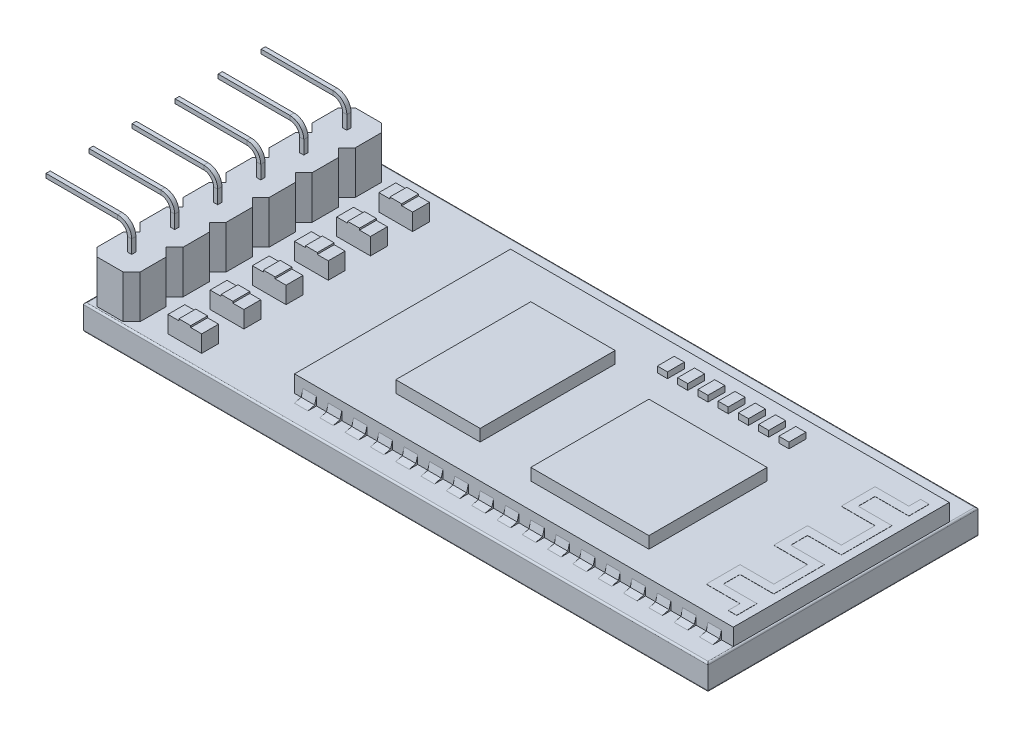
SolidWorks part; units mm, degrees
ref_plane "Front Plane" through (0, 0, 0) normal (0, 0, 1) x (1, 0, 0)
ref_plane "Top Plane" through (0, 0, 0) normal (0, 1, 0) x (1, 0, 0)
ref_plane "Right Plane" through (0, 0, 0) normal (1, 0, 0) x (0, 0, -1)
sketch "Sketch1" plane through (0, 0, 0) normal (0, 1, 0) x (1, 0, 0)
  line L1 (-18.5, -8) -> (18.5, -8)
  line L2 (-18.5, -8) -> (-18.5, 8)
  line L3 (-18.5, 8) -> (18.5, 8)
  line L4 (18.5, -8) -> (18.5, 8)
  line L5 (-18.5, -8) -> (18.5, 8) construction
  line L6 (-18.5, 8) -> (18.5, -8) construction
  point P0 (0, 0)
  dimension "D1" = 37
  dimension "D2" = 16
extrude "Boss-Extrude1" add sketch "Sketch1" along normal blind 1.5
sketch "Sketch2" plane through (0, 1.5, 0) normal (0, 1, 0) x (1, 0, 0)
  line L0 (18.5, 8) -> (-18.5, 8) construction
  line L1 (-17.9, 4.95) -> (-16.35, 4.95)
  line L2 (-18.4, 5.45) -> (-18.4, 7)
  line L3 (-17.9, 7.5) -> (-16.35, 7.5)
  line L4 (-15.85, 5.45) -> (-15.85, 7)
  line L5 (-18.4, 4.95) -> (-15.85, 7.5) construction
  line L6 (-18.4, 7.5) -> (-15.85, 4.95) construction
  line L7 (-18.5, 8) -> (-18.5, -8) construction
  line L8 (-16.35, 7.5) -> (-15.85, 7)
  line L9 (-16.35, 4.95) -> (-15.85, 5.45)
  line L10 (-18.4, 5.45) -> (-17.9, 4.95)
  line L11 (-18.4, 7) -> (-17.9, 7.5)
  point P0 (-17.125, 6.225)
  dimension "D1" = 2.55
  dimension "D2" = 2.55
  dimension "D3" = 0.5
  dimension "D4" = 0.1
extrude "Boss-Extrude2" add sketch "Sketch2" along normal blind 2.55
pattern_linear "LPattern1" count 6 spacing 2.55 along (0, 0, 1) of "Boss-Extrude2"
sketch "Sketch3" plane through (0, 4.05, 0) normal (0, 1, 0) x (1, 0, 0)
  line L0 (-16.35, 7.5) -> (-17.9, 7.5) construction
  line L1 (-18.4, 7) -> (-18.4, 5.45) construction
  point P0 (-17.125, 6.225)
  point P4 (-17.125, 7.5)
  point P9 (-18.4, 6.225)
ref_plane "Plane1" through (0, 0, -6.225) normal (0, 0, -1) x (-1, 0, 0)
sketch "Sketch4" plane through (0, 0, -6.225) normal (0, 0, -1) x (-1, 0, 0)
  line L0 (17.125, 4.05) -> (17.125, 4.85)
  line L1 (16.35, 4.05) -> (17.9, 4.05) construction
  line L2 (17.825, 5.55) -> (22.125, 5.55)
  arc A0 (17.125, 4.85) -> (17.825, 5.55) centre (17.825, 4.85) cw
  point P7 (17.125, 5.55)
  dimension "D3" = 0.7
  dimension "D1" = 1.5
  dimension "D2" = 5
sketch "Sketch5" plane through (0, 4.05, 0) normal (0, 1, 0) x (1, 0, 0)
  line L1 (-17.25, 6.1) -> (-17, 6.1)
  line L2 (-17.25, 6.1) -> (-17.25, 6.35)
  line L3 (-17.25, 6.35) -> (-17, 6.35)
  line L4 (-17, 6.1) -> (-17, 6.35)
  line L5 (-17.25, 6.1) -> (-17, 6.35) construction
  line L6 (-17.25, 6.35) -> (-17, 6.1) construction
  point P0 (-17.125, 6.225)
  dimension "D1" = 0.25
  dimension "D2" = 0.25
sweep "Sweep1" add profiles "Sketch5" path "Sketch4"
chamfer "Chamfer1" distance 0.05 angle 45 4 edges at (-22.125, 5.425, -6.225) (-22.125, 5.55, -6.35) (-22.125, 5.675, -6.225) (-22.125, 5.55, -6.1)
pattern_linear "LPattern2" count 6 spacing 2.55 along (0, 0, 1) of "Chamfer1", "Sweep1"
fillet "Fillet1" radius 0.1 8 edges at (0, 0, -8) (-18.5, 0, 0) (0, 0, 8) (18.5, 0, 0) (-18.5, 1.5, 0) (0, 1.5, -8) (18.5, 1.5, 0) (0, 1.5, 8)
sketch "Sketch6" plane through (0, 1.5, 0) normal (0, 1, 0) x (1, 0, 0)
  line L0 (18.4, -7.9) -> (18.4, 7.9) construction
  line L1 (18.4, 6.4) -> (-7.6, 6.4)
  line L2 (18.4, 6.4) -> (18.4, -6.4)
  line L3 (18.4, -6.4) -> (-7.6, -6.4)
  line L4 (-7.6, 6.4) -> (-7.6, -6.4)
  line L5 (18.4, 7.9) -> (-18.4, 7.9) construction
  line L6 (-18.4, -7.9) -> (18.4, -7.9) construction
  dimension "D1" = 1.5
  dimension "D2" = 1.5
  dimension "D3" = 26
extrude "Boss-Extrude3" add sketch "Sketch6" along normal blind 1
sketch "Sketch7" plane through (-7.6, 0, 0) normal (-1, 0, 0) x (0, 0, 1)
  line L0 (-6.9043, 1.5) -> (-6.5043, 1.6)
  line L1 (-6.4, 1.5) -> (-7.9, 1.5) construction
  line L2 (-6.5043, 1.6) -> (-6.4, 2)
  line L3 (-6.4, 2.5) -> (-6.4, 1.5) construction
  line L4 (-6.9043, 1.5) -> (-6.4, 1.5)
  line L5 (-6.4, 1.5) -> (-6.4, 2)
  line L6 (0, 1.5) -> (0, 2.5) construction
  line L7 (6.4, 1.5) -> (-6.4, 1.5) construction
  line L8 (-6.4, 2.5) -> (6.4, 2.5) construction
  line L9 (6.4, 1.5) -> (6.4, 2)
  line L10 (6.9043, 1.5) -> (6.4, 1.5)
  line L11 (6.5043, 1.6) -> (6.4, 2)
  line L12 (6.9043, 1.5) -> (6.5043, 1.6)
  dimension "D1" = 0.5043
  dimension "D2" = 0.1
  dimension "D3" = 0.4
extrude "Boss-Extrude4" add sketch "Sketch7" against normal blind 0.8 from offset 0.5 offset against normal yes
pattern_linear "LPattern3" count 17 spacing 1.5 along (1, 0, 0) of "Boss-Extrude4"
sketch "Sketch8" plane through (0, 2.5, 0) normal (0, 1, 0) x (1, 0, 0)
  line L0 (17.4, 5.7) -> (17.4, 5)
  line L2 (17.4, 5) -> (15.4, 5)
  line L3 (15.4, 5) -> (15.4, 3)
  line L4 (15.4, 3) -> (17.4, 3)
  line L5 (17.4, 3) -> (17.4, 1)
  line L6 (17.4, 1) -> (15.4, 1)
  line L7 (15.4, 1) -> (15.4, 0)
  line L8 (0, 0) -> (18.5, 0) construction
  line L9 (18.5, 8) -> (18.5, -8) construction
  line L10 (18.4, -6.4) -> (18.4, 6.4) construction
  line L11 (17.4, 5.7) -> (17.9, 5.7)
  line L12 (17.9, 5.2) -> (17.9, 5.2)
  line L13 (17.9, 5.7) -> (17.9, 4.5)
  line L14 (17.9, 4.5) -> (15.9, 4.5)
  line L15 (15.9, 4.5) -> (15.9, 3.5)
  line L16 (15.9, 3.5) -> (17.9, 3.5)
  line L17 (17.9, 3.5) -> (17.9, 0.5)
  line L18 (17.9, 0.5) -> (15.9, 0.5)
  line L19 (15.9, 0.5) -> (15.9, 0)
  line L20 (17.9, 5.2) -> (17.9, 4.5) construction
  line L21 (15.9, -0.5) -> (15.9, 0)
  line L22 (15.4, -1) -> (15.4, 0)
  line L23 (17.9, -0.5) -> (15.9, -0.5)
  line L24 (17.9, -3.5) -> (17.9, -0.5)
  line L25 (15.9, -3.5) -> (17.9, -3.5)
  line L26 (15.9, -4.5) -> (15.9, -3.5)
  line L27 (17.9, -4.5) -> (15.9, -4.5)
  line L28 (17.9, -5.7) -> (17.9, -4.5)
  line L29 (17.4, -5.7) -> (17.9, -5.7)
  line L30 (17.4, -1) -> (15.4, -1)
  line L31 (17.4, -3) -> (17.4, -1)
  line L32 (15.4, -3) -> (17.4, -3)
  line L33 (15.4, -5) -> (15.4, -3)
  line L34 (17.4, -5) -> (15.4, -5)
  line L35 (17.4, -5.7) -> (17.4, -5)
  dimension "D1" = 3
  dimension "D2" = 2
  dimension "D3" = 2
  dimension "D4" = 2
  dimension "D5" = 2
  dimension "D6" = 1
  dimension "D7" = 2
  dimension "D9" = 0.7
  dimension "D8" = 0.5
extrude "Boss-Extrude5" add sketch "Sketch8" along normal blind 0.01 contours L35 L29 L28 L27 L26 L25 L24 L23 L21 L19 L18 L17 L16 L15 L14 L13 L11 L0 L2 L3 L4 L5 L6 L7 L22 L30 L31 L32 L33 L34 region at (17.65, 2.5, -5.5833)
sketch "Sketch9" plane through (0, 1.5, 0) normal (0, 1, 0) x (1, 0, 0)
  line L0 (18.4, 7.9) -> (-18.4, 7.9) construction
  line L1 (-14.4, 5.4) -> (-12.4, 5.4)
  line L2 (-14.4, 5.4) -> (-14.4, 6.4)
  line L3 (-14.4, 6.4) -> (-12.4, 6.4)
  line L4 (-12.4, 5.4) -> (-12.4, 6.4)
  line L5 (-14.4, 5.4) -> (-12.4, 6.4) construction
  line L6 (-14.4, 6.4) -> (-12.4, 5.4) construction
  line L7 (-18.4, 5.45) -> (-18.4, 4.45) construction
  point P0 (-13.4, 5.9)
  dimension "D1" = 2
  dimension "D2" = 1
  dimension "D3" = 2
  dimension "D4" = 5
extrude "Boss-Extrude6" add sketch "Sketch9" along normal blind 1
sketch "Sketch10" plane through (0, 2.5, 0) normal (0, 1, 0) x (1, 0, 0)
  line L0 (-12.4, 6.4) -> (-14.4, 6.4) construction
  line L1 (-13.75, 5.4) -> (-13.05, 5.4)
  line L2 (-13.75, 5.4) -> (-13.75, 6.4)
  line L3 (-13.75, 6.4) -> (-13.05, 6.4)
  line L4 (-13.05, 5.4) -> (-13.05, 6.4)
  line L5 (-13.75, 5.4) -> (-13.05, 6.4) construction
  line L6 (-13.75, 6.4) -> (-13.05, 5.4) construction
  line L7 (-14.4, 6.4) -> (-14.4, 5.4) construction
  line L8 (-12.4, 6.4) -> (-14.4, 6.4) construction
  point P0 (-13.4, 5.9)
  point P8 (-13.4, 6.4)
  point P11 (-14.4, 5.9)
  dimension "D1" = 0.7
extrude "Boss-Extrude7" add sketch "Sketch10" along normal blind 0.1
pattern_linear "LPattern4" count 6 spacing 2.5 along (0, 0, 1) of "Boss-Extrude7", "Boss-Extrude6"
sketch "Sketch11" plane through (0, 2.5, 0) normal (0, 1, 0) x (1, 0, 0)
  line L0 (2.7, -6.4) -> (3.4, -6.4) construction
  line L1 (-3.6, -4.4) -> (1.4, -4.4)
  line L2 (-3.6, -4.4) -> (-3.6, 3.6)
  line L3 (-3.6, 3.6) -> (1.4, 3.6)
  line L4 (1.4, -4.4) -> (1.4, 3.6)
  line L5 (-3.6, -4.4) -> (1.4, 3.6) construction
  line L6 (-3.6, 3.6) -> (1.4, -4.4) construction
  line L7 (4.9, -4.9) -> (11.9, -4.9)
  line L8 (4.9, -4.9) -> (4.9, 2.1)
  line L9 (4.9, 2.1) -> (11.9, 2.1)
  line L10 (11.9, -4.9) -> (11.9, 2.1)
  line L11 (4.9, -4.9) -> (11.9, 2.1) construction
  line L12 (4.9, 2.1) -> (11.9, -4.9) construction
  line L13 (10.2, -6.4) -> (10.9, -6.4) construction
  line L14 (-7.6, 6.4) -> (-7.6, -6.4) construction
  point P0 (-1.1, -0.4)
  point P5 (8.4, -1.4)
  dimension "D1" = 5
  dimension "D2" = 8
  dimension "D3" = 6
  dimension "D4" = 7
  dimension "D5" = 7
  dimension "D6" = 1.5
  dimension "D7" = 4
  dimension "D8" = 3.5
extrude "Boss-Extrude8" add sketch "Sketch11" along normal blind 0.7
sketch "Sketch12" plane through (0, 2.5, 0) normal (0, 1, 0) x (1, 0, 0)
  line L0 (18.4, 6.4) -> (-7.6, 6.4) construction
  line L1 (3.1, 5.4) -> (3.7, 5.4)
  line L2 (3.1, 5.4) -> (3.1, 4.4)
  line L3 (3.1, 4.4) -> (3.7, 4.4)
  line L4 (3.7, 5.4) -> (3.7, 4.4)
  line L5 (3.1, 5.4) -> (3.7, 4.4) construction
  line L6 (3.1, 4.4) -> (3.7, 5.4) construction
  line L7 (-7.6, 6.4) -> (-7.6, -6.4) construction
  point P0 (3.4, 4.9)
  dimension "D1" = 0.6
  dimension "D2" = 1
  dimension "D3" = 1.5
  dimension "D4" = 11
extrude "Boss-Extrude9" add sketch "Sketch12" along normal blind 0.35
pattern_linear "LPattern5" count 7 spacing 1.2 along (1, 0, 0) of "Boss-Extrude9"
